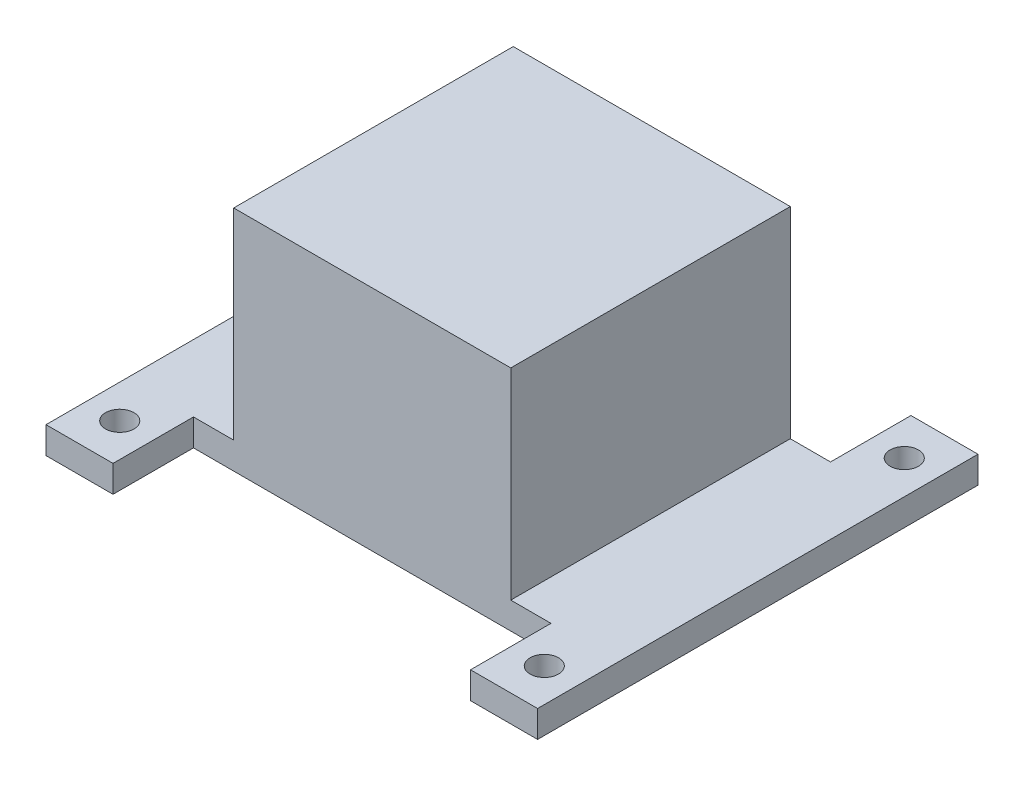
SolidWorks part; units mm, degrees
ref_plane "Front Plane" through (0, 0, 0) normal (0, 0, 1) x (1, 0, 0)
ref_plane "Top Plane" through (0, 0, 0) normal (0, 1, 0) x (1, 0, 0)
ref_plane "Right Plane" through (0, 0, 0) normal (1, 0, 0) x (0, 0, -1)
sketch "Sketch1" plane through (0, 0, 0) normal (0, 1, 0) x (1, 0, 0)
  line L1 (-55, -31.275) -> (55, -31.275)
  line L2 (-55, -31.275) -> (-55, 31.275)
  line L3 (-55, 31.275) -> (55, 31.275)
  line L4 (55, -31.275) -> (55, 31.275)
  line L5 (-55, -31.275) -> (55, 31.275) construction
  line L6 (-55, 31.275) -> (55, -31.275) construction
  point P0 (0, 0)
  dimension "D1" = 62.55
  dimension "D2" = 110
extrude "Boss-Extrude1" add sketch "Sketch1" along normal blind 6
sketch "Sketch2" plane through (0, 6, 0) normal (0, 1, 0) x (1, 0, 0)
  line L0 (0, 31.275) -> (0, -31.275) construction
  line L1 (55, 31.275) -> (-55, 31.275) construction
  line L2 (-55, -31.275) -> (55, -31.275) construction
  line L3 (-55, 2.725) -> (55, 2.725) construction
  line L4 (-55, 31.275) -> (-55, -31.275) construction
  line L5 (55, -31.275) -> (55, 31.275) construction
  circle A0 centre (0, 2.725) radius 9.5
  dimension "D1" = 19
  dimension "D2" = 55
  dimension "D3" = 34
extrude "Cut-Extrude1" cut sketch "Sketch2" against normal up to next
ref_axis "Axis1" through (0, 0, -2.725) along (0, 1, 0)
sketch "Sketch4" plane through (0, 0, 31.275) normal (0, 0, 1) x (1, 0, 0)
  line L0 (-55, 6) -> (55, 6) construction
  line L1 (-55, 0) -> (-40, 0)
  line L2 (-55, 0) -> (-55, 6)
  line L3 (-55, 6) -> (-40, 6)
  line L4 (-40, 0) -> (-40, 6)
  line L5 (0, -3.3) -> (0, 3.3) construction
  line L6 (55, 6) -> (40, 6)
  line L7 (40, 0) -> (40, 6)
  line L8 (55, 0) -> (40, 0)
  line L9 (55, 0) -> (55, 6)
  dimension "D1" = 15
extrude "Boss-Extrude2" add sketch "Sketch4" along normal blind 18
sketch "Sketch5" plane through (0, 6, 0) normal (0, 1, 0) x (1, 0, 0)
  line L0 (-47.5, -49.275) -> (-47.5, 31.275) construction
  line L1 (-40, -49.275) -> (-55, -49.275) construction
  line L2 (55, 31.275) -> (-55, 31.275) construction
  line L3 (0, -3.3) -> (0, 3.3) construction
  circle A0 centre (-47.5, -40.275) radius 3.175
  circle A1 centre (47.5, -40.275) radius 3.175
  dimension "D2" = 6.35
  dimension "D1" = 9
extrude "Cut-Extrude3" cut sketch "Sketch5" against normal blind 18
mirror "Mirror1" about plane through (0, 0, 0) normal (0, 0, 1) of "Boss-Extrude2", "Cut-Extrude3"
sketch "Sketch6" plane through (0, 6, 0) normal (0, 1, 0) x (1, 0, 0)
  line L0 (0, -31.275) -> (0, 31.275) construction
  line L1 (-40, -31.275) -> (40, -31.275) construction
  line L2 (40, 31.275) -> (-40, 31.275) construction
  line L3 (31, 31.275) -> (26, 31.275)
  line L4 (-31, -31.275) -> (-26, -31.275)
  line L5 (-31, -31.275) -> (-31, 31.275)
  line L6 (-31, 31.275) -> (-26, 31.275)
  line L7 (-26, -31.275) -> (-26, 31.275)
  line L8 (26, -31.275) -> (26, 31.275)
  line L9 (31, -31.275) -> (26, -31.275)
  line L10 (31, -31.275) -> (31, 31.275)
  dimension "D1" = 5
  dimension "D2" = 52
extrude "Boss-Extrude3" add sketch "Sketch6" along normal blind 40
sketch "Sketch7" plane through (31, 0, 0) normal (1, 0, 0) x (0, 0, -1)
  line L1 (-31.275, 46) -> (31.275, 46)
  line L2 (-31.275, 46) -> (-31.275, 51)
  line L3 (-31.275, 51) -> (31.275, 51)
  line L4 (31.275, 46) -> (31.275, 51)
  dimension "D1" = 5
  dimension "D2" = 62.55
extrude "Boss-Extrude4" add sketch "Sketch7" against normal up to surface (62 mm away) up to face at (-31, 26, 0)
sketch "Sketch8" plane through (0, 6, 0) normal (0, 1, 0) x (1, 0, 0)
  line L0 (26, 31.275) -> (26, -31.275) construction
  line L1 (26, -26.275) -> (-26, -26.275)
  line L2 (26, -26.275) -> (26, -31.275)
  line L3 (26, -31.275) -> (-26, -31.275)
  line L4 (-26, -26.275) -> (-26, -31.275)
  dimension "D1" = 5
extrude "Boss-Extrude5" add sketch "Sketch8" along normal up to next
sketch "Sketch9" plane through (0, 0, 26.275) normal (0, 0, -1) x (-1, 0, 0)
  line L0 (-26, 46) -> (-26, 6) construction
  line L1 (-26, 14) -> (-23, 14)
  line L2 (-26, 14) -> (-26, 16)
  line L3 (-26, 16) -> (-23, 16)
  line L4 (-23, 14) -> (-23, 16)
  line L5 (-26, 6) -> (26, 6) construction
  line L6 (-26, 17.6) -> (-23, 17.6)
  line L7 (-26, 17.6) -> (-26, 19.6)
  line L8 (-26, 19.6) -> (-23, 19.6)
  line L9 (-23, 17.6) -> (-23, 19.6)
  line L10 (-26, 26) -> (26, 26) construction
  line L11 (-26, 46) -> (-26, 6) construction
  line L12 (26, 46) -> (26, 6) construction
  line L13 (0, 6) -> (0, 46) construction
  line L14 (-26, 6) -> (26, 6) construction
  line L15 (26, 46) -> (-26, 46) construction
  line L16 (-26, 32.4) -> (-23, 32.4)
  line L17 (-23, 34.4) -> (-23, 32.4)
  line L18 (-26, 34.4) -> (-23, 34.4)
  line L19 (-26, 34.4) -> (-26, 32.4)
  line L20 (-26, 36) -> (-23, 36)
  line L21 (-23, 38) -> (-23, 36)
  line L22 (-26, 38) -> (-23, 38)
  line L23 (-26, 38) -> (-26, 36)
  line L24 (26, 16) -> (23, 16)
  line L25 (23, 14) -> (23, 16)
  line L26 (26, 14) -> (23, 14)
  line L27 (26, 14) -> (26, 16)
  line L28 (26, 19.6) -> (23, 19.6)
  line L29 (23, 17.6) -> (23, 19.6)
  line L30 (26, 17.6) -> (23, 17.6)
  line L31 (26, 17.6) -> (26, 19.6)
  line L32 (26, 34.4) -> (26, 32.4)
  line L33 (26, 34.4) -> (23, 34.4)
  line L34 (23, 34.4) -> (23, 32.4)
  line L35 (26, 32.4) -> (23, 32.4)
  line L36 (26, 38) -> (26, 36)
  line L37 (26, 38) -> (23, 38)
  line L38 (23, 38) -> (23, 36)
  line L39 (26, 36) -> (23, 36)
  point P10 (-24.5, 17.6)
  dimension "D1" = 3
  dimension "D2" = 2
  dimension "D3" = 1.6
  dimension "D4" = 3
  dimension "D5" = 2
  dimension "D6" = 8
